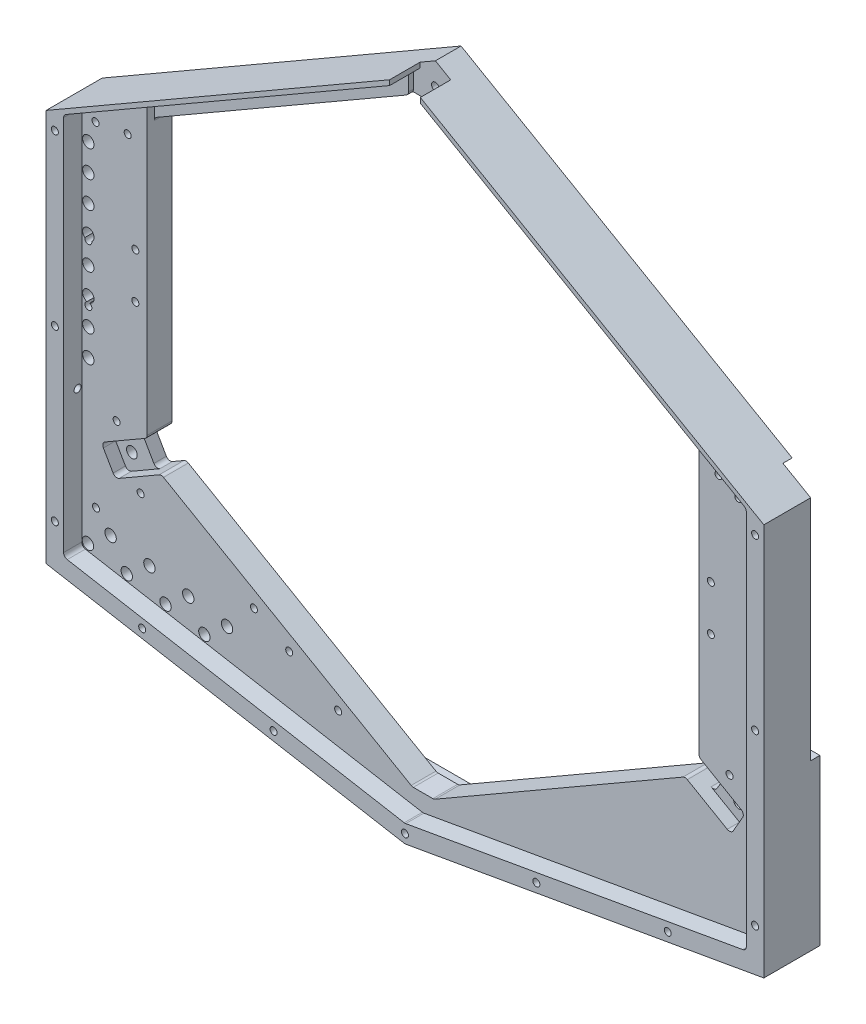
SolidWorks part; units mm, degrees
material "Copper"
ref_plane "Front Plane" through (0, 0, 0) normal (0, 0, 1) x (1, 0, 0)
ref_plane "Top Plane" through (0, 0, 0) normal (0, 1, 0) x (1, 0, 0)
ref_plane "Right Plane" through (0, 0, 0) normal (1, 0, 0) x (0, 0, -1)
sketch "Sketch2" plane through (0, 0, 0) normal (0, 0, 1) x (1, 0, 0)
  line L0 (-81.94, 26.6174) -> (0, 73.9255)
  line L1 (0, 73.9255) -> (81.94, 26.6174)
  line L2 (81.94, 26.6174) -> (81.94, -62.9963)
  line L3 (81.94, -62.9963) -> (0, -77.4445)
  line L4 (0, -77.4445) -> (-81.94, -62.9963)
  line L5 (-81.94, -62.9963) -> (-81.94, 26.6174)
  dimension "D1" = 120
  dimension "D2" = 120
  dimension "D3" = 160
  dimension "D4" = 151.37
  dimension "D5" = 163.88
extrude "Outline" add sketch "Sketch2" against normal blind 12.8
sketch "Sketch3" plane through (0, 0, 0) normal (0, 0, 1) x (1, 0, 0)
  line L0 (-77.94, 27.7721) -> (0, 72.7708)
  line L1 (0, 72.7708) -> (77.94, 27.7721)
  line L2 (77.94, 27.7721) -> (77.94, -59.6399)
  line L3 (77.94, -59.6399) -> (0, -73.3828)
  line L4 (0, -73.3828) -> (-77.94, -59.6399)
  line L5 (-77.94, -59.6399) -> (-77.94, 27.7721)
  line L12 (0, 73.9255) -> (-81.94, 26.6174) construction
  line L14 (0, -77.4445) -> (81.94, -62.9963) construction
  line L15 (-81.94, -62.9963) -> (0, -77.4445) construction
  line L16 (81.94, 26.6174) -> (0, 73.9255) construction
  line L17 (81.94, -62.9963) -> (81.94, 26.6174) construction
  line L18 (-81.94, 26.6174) -> (-81.94, -62.9963) construction
  dimension "D1" = 1
  dimension "D2" = 1
  dimension "D3" = 4
  dimension "D4" = 4
  dimension "D5" = 4
  dimension "D6" = 4
extrude "Inside Cutout" cut sketch "Sketch3" against normal blind 4.14
sketch "Reference Center Line" plane through (0, 0, -4.14) normal (0, 0, 1) x (1, 0, 0)
  line L0 (0, 73.9255) -> (0, -77.4445) construction
  line L1 (-62.3538, 35.1699) -> (0, 71.1699) construction
  line L2 (0, -70.1165) -> (62.3538, -34.1165) construction
  line L3 (62.3538, -34.1165) -> (62.3538, 37.8835) construction
  line L4 (62.3538, 37.8835) -> (0, 73.8835) construction
  line L5 (0, 73.8835) -> (-62.3538, 37.8835) construction
  line L6 (-62.3538, 37.8835) -> (-62.3538, -34.1165) construction
  line L7 (-62.3538, -34.1165) -> (0, -70.1165) construction
  line L8 (0, 71.1699) -> (62.3538, 35.1699) construction
  line L9 (-3.4641, 69.1699) -> (3.4641, 69.1699) construction
  line L11 (-46, 33.8928) -> (46, 33.8928) construction
  line L12 (-46, 33.8928) -> (-46, -62.2855) construction
  line L13 (-46, -62.2855) -> (46, -62.2855) construction
  line L14 (46, 33.8928) -> (46, -62.2855) construction
  circle A0 centre (0, 1.8835) radius 62.3538 construction
  circle A1 centre (0, 1.8835) radius 0.4741 construction
  point P22 (0, 33.8928)
  dimension "D1" = 72
  dimension "D2" = 72.042
  dimension "D3" = 2.35
  dimension "D4" = 2
  dimension "D5" = 92
sketch "Sketch5" plane through (0, 0, -12.8) normal (0, 0, -1) x (-1, 0, 0)
  line L0 (0, -70.8942) -> (-63, -34.5211)
  line L1 (-63, -34.5211) -> (-63, 31.7789)
  line L2 (5, 65.2652) -> (5, 69.884)
  line L3 (0, 0) -> (0, 50) construction
  line L6 (5, 69.884) -> (0, 72.7708)
  line L8 (0, 72.7708) -> (77.94, 27.7721) construction
  line L9 (63, 31.7789) -> (63, -34.5211)
  line L10 (63, -34.5211) -> (0, -70.8942)
  line L11 (0, 72.7708) -> (-5, 69.884)
  line L21 (5, 65.2652) -> (63, 31.7789)
  line L32 (0, 73.9255) -> (0, -77.4445) construction
  line L33 (-5, 69.884) -> (-5, 65.2652)
  line L34 (-77.94, 27.7721) -> (0, 72.7708) construction
  line L35 (-63, 31.7789) -> (-5, 65.2652)
  line L36 (0, 73.9255) -> (0, 1.8855) construction
  line L37 (0, 1.8855) -> (69.308, -38.1295) construction
  line L38 (0, 1.8855) -> (-69.308, -38.1295) construction
  dimension "D1" = 4
  dimension "D2" = 10
  dimension "D3" = 126
  dimension "D4" = 66.3
  dimension "D5" = 66.3
  dimension "D6" = 5
  dimension "D7" = 50
  dimension "D8" = 72.04
  dimension "D9" = 120
  dimension "D10" = 120
  dimension "D11" = 80.03
  dimension "D12" = 80.03
extrude "Cut for Spring Base" cut sketch "Sketch5" against normal through all
sketch "Sketch7" plane through (0, 0, -12.8) normal (0, 0, -1) x (-1, 0, 0)
  line L0 (-5, 69.884) -> (0, 72.7708)
  line L2 (0, 72.7708) -> (5, 69.884)
  line L4 (5, 69.884) -> (5, 60.7708)
  line L5 (5, 60.7708) -> (-5, 60.7708)
  line L6 (-5, 60.7708) -> (-5, 69.884)
  line L7 (-77.94, 27.7721) -> (0, 72.7708) construction
  line L8 (0, 73.9255) -> (0, -77.4445) construction
  line L9 (-77.94, 27.7721) -> (-5, 69.884) construction
  line L10 (5, 69.884) -> (77.94, 27.7721) construction
  dimension "D2" = 12
  dimension "D3" = 10
extrude "J Flex Mounting Point" add sketch "Sketch7" against normal offset from surface (5.85 mm away) 2.81 up to face at (0, 4.0573, -4.14)
sketch "Sketch6" plane through (0, 0, -12.8) normal (0, 0, -1) x (-1, 0, 0)
  line L0 (-67.5, 33.7996) -> (-67.5, -37.6965)
  line L2 (10, -70.8942) -> (67.5, -37.6965)
  line L3 (67.5, -37.6965) -> (67.5, 33.7996)
  line L9 (-10, -70.8942) -> (0, -70.8942)
  line L10 (-63, 31.7789) -> (-63, -34.5211) construction
  line L11 (63, -34.5211) -> (63, 31.7789) construction
  line L12 (0, -70.8942) -> (63, -34.5211) construction
  line L19 (67.5, 33.7996) -> (0, 72.7708)
  line L20 (77.94, 27.7721) -> (0, 72.7708) construction
  line L21 (0, 72.7708) -> (-77.94, 27.7721) construction
  line L22 (0, 72.7708) -> (-67.5, 33.7996)
  line L47 (0, -70.8942) -> (10, -70.8942)
  line L48 (-67.5, -37.6965) -> (-10, -70.8942)
  line L50 (-63, -34.5211) -> (0, -70.8942) construction
  line L52 (0, 73.9255) -> (0, -77.4445) construction
  dimension "D1" = 4.5
  dimension "D2" = 4.5
  dimension "D3" = 5
  dimension "D4" = 5
extrude "Spring Base Mounting Cut" cut sketch "Sketch6" against normal blind 3
sketch "Sketch9" plane through (0, 0, 0) normal (0, 0, 1) x (1, 0, 0)
  line L2 (3.5, 71.9048) -> (3.5, 70.7501)
  line L3 (77.94, 27.7721) -> (0, 72.7708) construction
  line L4 (3.5, 70.7501) -> (0, 72.7708)
  line L5 (0, 72.7708) -> (-3.5, 70.7501)
  line L6 (0, 72.7708) -> (-77.94, 27.7721) construction
  line L7 (-3.5, 70.7501) -> (-3.5, 71.9048)
  line L10 (-3.5, 71.9048) -> (0, 73.9255)
  line L11 (0, 73.9255) -> (0, -77.4445) construction
  line L12 (0, 73.9255) -> (3.5, 71.9048)
  line L14 (0, 73.9255) -> (-81.94, 26.6174) construction
  dimension "D1" = 7
extrude "Central Copper Flex cutout" cut sketch "Sketch9" against normal up to surface (6.95 mm away) up to face at (0, 66.373, -6.95)
hole_wizard "M2 Tap Drill for Backplate" positions "Sketch10" profile "Sketch11" hole size "M2x0.4" standard "ANSI Metric"
sketch "Sketch10" plane through (0, 0, -9.8) normal (0, 0, -1) x (-1, 0, 0)
  line L0 (-65, 24.3042) -> (-65, -35.6758) construction
  line L1 (-65, -35.6758) -> (-4, -70.8942) construction
  line L2 (-10, -70.8942) -> (10, -70.8942) construction
  line L4 (4, -70.8942) -> (65, -35.6758) construction
  line L5 (65, -35.6758) -> (65, 24.3242) construction
  line L7 (-63, -34.5211) -> (-63, 31.7789) construction
  line L8 (63, 31.7789) -> (63, -34.5211) construction
  line L9 (63, -34.5211) -> (0, -70.8942) construction
  line L10 (0, -70.8942) -> (-63, -34.5211) construction
  line L29 (-62.3538, 33.884) -> (0, 69.884) construction
  line L30 (-62.3538, -34.1165) -> (-62.3538, 37.8835) construction
  line L31 (0, 73.9255) -> (0, -77.4445) construction
  line L32 (0, 69.884) -> (62.3538, 33.884) construction
  line L33 (62.3538, 37.8835) -> (62.3538, -34.1165) construction
  line L36 (5, 65.2652) -> (63, 31.7789) construction
  line L37 (-63, 31.7789) -> (-5, 65.2652) construction
  line L38 (-63, -34.5211) -> (-67.5, -37.6965) construction
  point P0 (-65, 24.3042)
  point P2 (-41.1362, 46.134)
  point P4 (-19.4856, 58.634)
  point P6 (19.4856, 58.634)
  point P8 (41.1362, 46.134)
  point P10 (65, 24.3242)
  point P12 (65, 1.8242)
  point P14 (65, -20.6758)
  point P18 (52.0096, -43.1758)
  point P20 (32.9571, -54.1758)
  point P22 (15.6366, -64.1758)
  point P24 (-15.6366, -64.1758)
  point P26 (-32.9571, -54.1758)
  point P28 (-52.0096, -43.1758)
  point P32 (-65, -20.6958)
  point P35 (-65, 1.8042)
  dimension "D1" = 2
  dimension "D2" = 2
  dimension "D3" = 2
  dimension "D4" = 2
  dimension "D5" = 14.98
  dimension "D6" = 22.5
  dimension "D7" = 22.5
  dimension "D8" = 15
  dimension "D9" = 22
  dimension "D10" = 20
  dimension "D11" = 20
  dimension "D12" = 22
  dimension "D13" = 15
  dimension "D14" = 22.5
  dimension "D15" = 22.5
  dimension "D16" = 15
  dimension "D17" = 1.5
  dimension "D18" = 22.5
  dimension "D19" = 25
  dimension "D20" = 22.5
  dimension "D21" = 25
sketch "Sketch11" plane through (65, 24.3042, -9.8) normal (1, 0, 0) x (0, 1, 0)
  line L0 (0, 0) -> (0, 3.9807)
  line L1 (0, 3.9807) -> (0.8, 3.5)
  line L2 (0.8, 3.5) -> (0.8, 0)
  line L5 (0.8, 0) -> (0, 0)
  line L10 (0, 3.9807) -> (-0.8, 3.5) construction
  line L11 (0, -6.35) -> (0, 107.95) construction
  dimension "Hole Dia." = 1.6
  dimension "Hole Depth" = 3.5
  dimension "Drill Angle" = 118
sketch "Sketch12" plane through (0, 0, -12.8) normal (0, 0, -1) x (-1, 0, 0)
  line L0 (10, -70.8942) -> (67.5, -37.6965) construction
  line L1 (64, -39.7172) -> (67.5, -37.6965)
  line L2 (67.5, -37.6965) -> (67.5, -33.6551)
  line L3 (67.5, -37.6965) -> (67.5, 33.7996) construction
  line L4 (67.5, -33.6551) -> (74.4462, -37.6654)
  line L5 (74.4462, -37.6654) -> (70.9462, -43.7276)
  line L6 (70.9462, -43.7276) -> (64, -39.7172)
  line L7 (-67.5, -33.6551) -> (-67.5, -37.6965)
  line L8 (-67.5, 33.7996) -> (-67.5, -37.6965) construction
  line L9 (-67.5, -37.6965) -> (-64, -39.7172)
  line L10 (-67.5, -37.6965) -> (-10, -70.8942) construction
  line L11 (-64, -39.7172) -> (-70.9462, -43.7276)
  line L12 (-70.9462, -43.7276) -> (-74.4462, -37.6654)
  line L13 (-74.4462, -37.6654) -> (-67.5, -33.6551)
  dimension "D1" = 60
  dimension "D2" = 6
  dimension "D3" = 7
  dimension "D4" = 6
  dimension "D5" = 7
extrude "Outer Copper Flex cutouts" cut sketch "Sketch12" against normal up to surface (3 mm away) up to face at (64.2, 24.3042, -9.8)
hole_wizard "#2 Clearance Holes for Flex Feet" positions "Sketch13" profile "Sketch14" hole size "#2" standard "ANSI Inch"
sketch "Sketch13" plane through (0, 0, -9.8) normal (0, 0, -1) x (-1, 0, 0)
  line L1 (0, 1.8835) -> (69.3037, -38.129) construction
  line L3 (0, 1.8835) -> (-69.308, -38.1315) construction
  line L5 (0, 73.9255) -> (0, -77.4445) construction
  point P0 (69.3037, -38.129)
  point P3 (-69.308, -38.1315)
  point P6 (0, 68.6855)
  point P29 (0, 0)
  dimension "D1" = 66.802
  dimension "D2" = 80.025
  dimension "D3" = 60
  dimension "D4" = 60
  dimension "D5" = 80.03
sketch "Sketch14" plane through (-69.3037, -38.129, -9.8) normal (1, 0, 0) x (0, 1, 0)
  line L0 (0, 0) -> (0, 5.66)
  line L1 (0, 5.66) -> (1.2192, 5.66)
  line L2 (1.2192, 5.66) -> (1.2192, 0)
  line L5 (1.2192, 0) -> (0, 0)
  line L11 (0, -6.35) -> (0, 107.95) construction
  dimension "Thru Hole Dia." = 2.4384
  dimension "Thru Hole Depth" = 5.66
sketch "Sketch15" plane through (0, 0, -4.14) normal (0, 0, 1) x (1, 0, 0)
  line L0 (-63, -30.7945) -> (-73.5018, -36.8577)
  line L1 (-63, 31.7789) -> (-63, -34.5211) construction
  line L2 (-73.5018, -36.8577) -> (-70.2745, -42.4476)
  line L3 (-70.2745, -42.4476) -> (-59.7727, -36.3844)
  line L4 (-63, -34.5211) -> (0, -70.8942) construction
  line L5 (-59.7727, -36.3844) -> (-63, -34.5211)
  line L6 (-63, -34.5211) -> (-63, -30.7945)
  line L7 (-64.6136, -31.7262) -> (-61.3864, -37.316) construction
  line L8 (63, -34.5211) -> (63, -30.8575)
  line L9 (63, -34.5211) -> (63, 31.7789) construction
  line L10 (63, -30.8575) -> (73.4788, -36.9075)
  line L11 (73.4788, -36.9075) -> (70.3061, -42.4028)
  line L12 (70.3061, -42.4028) -> (59.8273, -36.3529)
  line L13 (0, -70.8942) -> (63, -34.5211) construction
  line L14 (59.8273, -36.3529) -> (63, -34.5211)
  point P12 (-63, -34.5211)
  dimension "D1" = 3.2
  dimension "D2" = 3
  dimension "D3" = 3.2
  dimension "D4" = 3
extrude "Channels for Outer Flex" cut sketch "Sketch15" against normal up to surface (2.81 mm away) up to face at (0, 68.2796, -6.95)
sketch "Sketch17" plane through (0, 0, -9.8) normal (0, 0, -1) x (-1, 0, 0)
  line L0 (-65, 1.8042) -> (-65, -20.6958) construction
  line L1 (65, -20.6758) -> (65, 1.8242) construction
  circle A0 centre (-65, -9.4458) radius 0.8
  circle A1 centre (65, -9.4258) radius 0.8
  dimension "D1" = 1.6
  dimension "D2" = 1.6
extrude "Optional Alignment Pins" cut sketch "Sketch17" against normal blind 3
sketch "SMA Reference Sketch" plane through (0, 0, -12.8) normal (0, 0, -1) x (-1, 0, 0)
  line L14 (81.94, 26.6174) -> (81.94, -62.9963) construction
  line L21 (73.8944, 19.163) -> (78.9856, 14.0718) construction
  line L22 (73.8944, 23.663) -> (78.9856, 18.5718) construction
  line L23 (73.8944, 14.663) -> (78.9856, 9.5718) construction
  line L24 (73.8944, 10.163) -> (78.9856, 5.0718) construction
  line L25 (72.1444, -32.8014) -> (77.2356, -37.8926) construction
  line L26 (-73.8944, 20.0718) -> (-78.9856, 25.163) construction
  line L27 (-81.94, -62.9963) -> (-81.94, 26.6174) construction
  line L28 (-73.8944, 15.5718) -> (-78.9856, 20.663) construction
  line L29 (-73.8944, 11.0718) -> (-78.9856, 16.163) construction
  line L30 (-73.8944, 6.5718) -> (-78.9856, 11.663) construction
  line L31 (59.1444, -57.3926) -> (64.2356, -52.3014) construction
  line L32 (72.1444, -50.8926) -> (77.2356, -45.8014) construction
  line L33 (72.1444, -93.8926) -> (77.2356, -88.8014) construction
  line L34 (-73.8944, 2.0718) -> (-78.9856, 7.163) construction
  line L35 (-73.8944, -2.4282) -> (-78.9856, 2.663) construction
  line L36 (-73.8944, -6.9282) -> (-78.9856, -1.837) construction
  line L37 (-73.8944, -11.4282) -> (-78.9856, -6.337) construction
  line L38 (73.8944, 5.663) -> (78.9856, 0.5718) construction
  line L39 (73.8944, 1.163) -> (78.9856, -3.9282) construction
  line L40 (73.8944, -3.337) -> (78.9856, -8.4282) construction
  line L41 (73.8944, -7.837) -> (78.9856, -12.9282) construction
  circle A0 centre (73.8944, 23.663) radius 0.95 construction
  circle A1 centre (78.9856, 18.5718) radius 0.95 construction
  circle A2 centre (76.44, 21.1174) radius 1.3 construction
  circle A3 centre (73.8944, 19.163) radius 0.95 construction
  circle A4 centre (78.9856, 14.0718) radius 0.95 construction
  circle A5 centre (76.44, 16.6174) radius 1.3 construction
  circle A6 centre (73.8944, 14.663) radius 0.95 construction
  circle A7 centre (78.9856, 9.5718) radius 0.95 construction
  circle A8 centre (76.44, 12.1174) radius 1.3 construction
  circle A9 centre (73.8944, 10.163) radius 0.95 construction
  circle A10 centre (78.9856, 5.0718) radius 0.95 construction
  circle A11 centre (76.44, 7.6174) radius 1.3 construction
  circle A12 centre (72.1444, -32.8014) radius 0.95 construction
  circle A13 centre (77.2356, -37.8926) radius 0.95 construction
  circle A14 centre (74.69, -35.347) radius 1.3 construction
  circle A15 centre (-76.44, 22.6174) radius 1.3 construction
  circle A16 centre (-78.9856, 25.163) radius 0.95 construction
  circle A17 centre (-73.8944, 20.0718) radius 0.95 construction
  circle A18 centre (-76.44, 18.1174) radius 1.3 construction
  circle A19 centre (-78.9856, 20.663) radius 0.95 construction
  circle A20 centre (-73.8944, 15.5718) radius 0.95 construction
  circle A21 centre (-76.44, 13.6174) radius 1.3 construction
  circle A22 centre (-78.9856, 16.163) radius 0.95 construction
  circle A23 centre (-73.8944, 11.0718) radius 0.95 construction
  circle A24 centre (-76.44, 9.1174) radius 1.3 construction
  circle A25 centre (-78.9856, 11.663) radius 0.95 construction
  circle A26 centre (-73.8944, 6.5718) radius 0.95 construction
  circle A27 centre (61.69, -54.847) radius 1.3 construction
  circle A28 centre (64.2356, -52.3014) radius 0.95 construction
  circle A29 centre (59.1444, -57.3926) radius 0.95 construction
  circle A30 centre (72.1444, -50.8926) radius 0.95 construction
  circle A31 centre (77.2356, -45.8014) radius 0.95 construction
  circle A32 centre (74.69, -48.347) radius 1.3 construction
  circle A33 centre (74.69, -91.347) radius 1.3 construction
  circle A34 centre (77.2356, -88.8014) radius 0.95 construction
  circle A35 centre (72.1444, -93.8926) radius 0.95 construction
  circle A36 centre (74.69, -35.347) radius 43 construction
  circle A37 centre (74.69, -48.347) radius 13 construction
  circle A38 centre (61.69, -54.847) radius 43 construction
  circle A39 centre (74.69, -91.347) radius 43 construction
  circle A40 centre (76.44, 21.1174) radius 13 construction
  circle A41 centre (-76.44, 4.6174) radius 1.3 construction
  circle A42 centre (-78.9856, 7.163) radius 0.95 construction
  circle A43 centre (-73.8944, 2.0718) radius 0.95 construction
  circle A44 centre (-76.44, 0.1174) radius 1.3 construction
  circle A45 centre (-78.9856, 2.663) radius 0.95 construction
  circle A46 centre (-73.8944, -2.4282) radius 0.95 construction
  circle A47 centre (-76.44, -4.3826) radius 1.3 construction
  circle A48 centre (-78.9856, -1.837) radius 0.95 construction
  circle A49 centre (-73.8944, -6.9282) radius 0.95 construction
  circle A50 centre (-76.44, -8.8826) radius 1.3 construction
  circle A51 centre (-78.9856, -6.337) radius 0.95 construction
  circle A52 centre (-73.8944, -11.4282) radius 0.95 construction
  circle A53 centre (73.8944, 5.663) radius 0.95 construction
  circle A54 centre (78.9856, 0.5718) radius 0.95 construction
  circle A55 centre (76.44, 3.1174) radius 1.3 construction
  circle A56 centre (73.8944, 1.163) radius 0.95 construction
  circle A57 centre (78.9856, -3.9282) radius 0.95 construction
  circle A58 centre (76.44, -1.3826) radius 1.3 construction
  circle A59 centre (73.8944, -3.337) radius 0.95 construction
  circle A60 centre (78.9856, -8.4282) radius 0.95 construction
  circle A61 centre (76.44, -5.8826) radius 1.3 construction
  circle A62 centre (73.8944, -7.837) radius 0.95 construction
  circle A63 centre (78.9856, -12.9282) radius 0.95 construction
  circle A64 centre (76.44, -10.3826) radius 1.3 construction
  point P10 (76.44, 16.6174)
  point P20 (76.44, 21.1174)
  point P25 (76.44, 12.1174)
  point P32 (76.44, 7.6174)
  point P37 (74.69, -35.347)
  point P120 (76.44, 3.1174)
  point P127 (76.44, -1.3826)
  point P134 (76.44, -5.8826)
  point P141 (76.44, -10.3826)
  dimension "D5" = 1.9
  dimension "D2" = 2.6
  dimension "D3" = 8
  dimension "D10" = 2.6
  dimension "D11" = 1.9
  dimension "D12" = 1.9
  dimension "D18" = 26
  dimension "D23" = 86
  dimension "D26" = 4.5
  dimension "D27" = 4.5
  dimension "D28" = 4.5
  dimension "D29" = 43
  dimension "D30" = 13
  dimension "D31" = 26
  dimension "D1" = 7.2
  dimension "D4" = 4.5
  dimension "D6" = 5.5
  dimension "D7" = 5.5
  dimension "D8" = 45
  dimension "D9" = 7.25
  dimension "D13" = 7.2
  dimension "D14" = 5.5
  dimension "D15" = 4
  dimension "D16" = 45
  dimension "D19" = 7.25
  dimension "D20" = 45
  dimension "D21" = 4.5
  dimension "D22" = 7.25
  dimension "D24" = 13
  dimension "D25" = 43
  dimension "D17" = 8
sketch "Sketch19" plane through (0, 0, -12.8) normal (0, 0, -1) x (-1, 0, 0)
  line L1 (81.94, -62.9963) -> (0, -77.4445) construction
  circle A0 centre (76.44, 21.1174) radius 1.3
  circle A12 centre (-76.44, 22.6174) radius 1.3
  circle A22 centre (-76.44, 16.5174) radius 1.3
  circle A23 centre (-76.44, 10.4174) radius 1.3
  circle A24 centre (-76.44, 4.3174) radius 1.3
  circle A25 centre (-76.44, -1.7826) radius 1.3
  circle A26 centre (-76.44, -7.8826) radius 1.3
  circle A27 centre (-76.44, -13.9826) radius 1.3
  circle A28 centre (-76.44, -20.0826) radius 1.3
  circle A29 centre (76.44, 15.0174) radius 1.3
  circle A30 centre (76.44, 8.9174) radius 1.3
  circle A31 centre (76.44, 2.8174) radius 1.3
  circle A32 centre (76.44, -3.2826) radius 1.3
  circle A33 centre (76.44, -9.3826) radius 1.3
  circle A34 centre (76.44, -15.4826) radius 1.3
  circle A35 centre (76.44, -21.5826) radius 1.3
  circle A36 centre (49.94, -63.0539) radius 1.3
  circle A44 centre (44.763, -58.8896) radius 1.3
  circle A50 centre (53.6263, -57.3268) radius 1.3
  circle A51 centre (58.8033, -61.4911) radius 1.3
  circle A52 centre (62.4895, -55.7639) radius 1.3
  circle A53 centre (67.6665, -59.9282) radius 1.3
  circle A54 centre (71.3528, -54.2011) radius 1.3
  circle A55 centre (76.5298, -58.3654) radius 1.3
  dimension "D1" = 2.6
  dimension "D2" = 8
  dimension "D3" = 8
  dimension "D4" = 5.5
  dimension "D5" = 32
  dimension "D6" = 4
  dimension "D7" = 10.5
  dimension "D8" = 6.644
extrude "SMA_Lines" cut sketch "Sketch19" against normal up to next
sketch "Sketch20" plane through (0, 0, -12.8) normal (0, 0, -1) x (-1, 0, 0)
  line L0 (67.5, 23.8447) -> (73.0812, 29.4259)
  line L1 (67.5, -33.6551) -> (67.5, 33.7996) construction
  line L2 (42.44, -52.1649) -> (37.6769, -54.9149)
  line L3 (73.0812, 29.4259) -> (81.94, 20.5672)
  line L4 (81.94, 20.5672) -> (81.94, -62.9963)
  line L5 (81.94, -62.9963) -> (42.44, -69.9612)
  line L6 (81.94, -62.9963) -> (0, -77.4445) construction
  line L8 (10, -70.8942) -> (64, -39.7172) construction
  line L9 (10, -70.8942) -> (64, -39.7172) construction
  line L10 (42.44, -52.1649) -> (64, -39.7172)
  line L11 (64, -39.7172) -> (67.5, -33.6551)
  line L12 (67.5, -33.6551) -> (74.4462, -37.6654) construction
  line L13 (67.5, -33.6551) -> (67.5, 23.8447)
  line L14 (-75.6096, 30.2723) -> (-67.5, 22.1627)
  line L15 (-81.94, 26.6174) -> (0, 73.9255) construction
  line L16 (-67.5, 33.7996) -> (-67.5, -33.6551) construction
  line L17 (-67.5, 22.1627) -> (-67.5, -25.3826)
  line L18 (-67.5, -25.3826) -> (-81.94, -25.3826)
  line L20 (-81.94, -62.9963) -> (-81.94, 26.6174) construction
  line L21 (-81.94, -25.3826) -> (-81.94, 26.6174)
  line L22 (-81.94, 26.6174) -> (-75.6096, 30.2723)
  line L23 (73.8944, 23.663) -> (78.9856, 18.5718) construction
  line L24 (-73.8944, 20.0718) -> (-78.9856, 25.163) construction
  line L25 (37.6769, -54.9149) -> (37.6769, -58.9149)
  line L26 (37.6769, -58.9149) -> (42.44, -58.9149)
  line L28 (42.44, -58.9149) -> (42.44, -69.9612)
  dimension "D2" = 8.25
  dimension "D3" = 6
  dimension "D4" = 34.5
  dimension "D5" = 3.5
extrude "SMA Cutaway" cut sketch "Sketch20" against normal offset from surface (2.11 mm away) 6.55 up to face at (77.74, 22.6174, -4.14)
fillet "Fillet4" radius 3 2 edges at (-73.0812, 29.4259, -11.745) (-37.6769, -58.9149, -11.745)
hole_wizard "M2x0.4 Tapped for SMAs" positions "Sketch21" profile "Sketch22" hole size "M2x0.4" standard "ANSI Metric"
sketch "Sketch21" plane through (0, 0, -10.69) normal (0, 0, -1) x (-1, 0, 0)
  circle A0 centre (76.44, 21.1174) radius 1.3 construction
  circle A1 centre (-76.44, 22.6174) radius 1.3 construction
  circle A2 centre (49.94, -63.0539) radius 1.3 construction
  circle A3 centre (44.763, -58.8896) radius 1.3 construction
  point P72 (73.895, 23.6624)
  point P74 (78.985, 18.5724)
  point P90 (-78.985, 25.1624)
  point P92 (-73.895, 20.0724)
  point P108 (-78.985, 19.0624)
  point P109 (-73.895, 13.9724)
  point P110 (-78.985, 12.9624)
  point P111 (-73.895, 7.8724)
  point P112 (-78.985, 6.8624)
  point P113 (-73.895, 1.7724)
  point P114 (-78.985, 0.7624)
  point P115 (-73.895, -4.3276)
  point P116 (-78.985, -5.3376)
  point P117 (-73.895, -10.4276)
  point P118 (-78.985, -11.4376)
  point P119 (-73.895, -16.5276)
  point P120 (-78.985, -17.5376)
  point P121 (-73.895, -22.6276)
  point P138 (73.895, 17.5624)
  point P139 (78.985, 12.4724)
  point P140 (73.895, 11.4624)
  point P141 (78.985, 6.3724)
  point P142 (73.895, 5.3624)
  point P143 (78.985, 0.2724)
  point P144 (73.895, -0.7376)
  point P145 (78.985, -5.8276)
  point P146 (73.895, -6.8376)
  point P147 (78.985, -11.9276)
  point P148 (73.895, -12.9376)
  point P149 (78.985, -18.0276)
  point P150 (73.895, -19.0376)
  point P151 (78.985, -24.1276)
  point P171 (49.315, -59.5089)
  point P173 (50.565, -66.5989)
  point P185 (58.1783, -57.9461)
  point P186 (59.4283, -65.0361)
  point P187 (67.0415, -56.3832)
  point P188 (68.2915, -63.4732)
  point P189 (75.9048, -54.8204)
  point P190 (77.1548, -61.9104)
  point P191 (45.388, -62.4346)
  point P193 (44.138, -55.3446)
  point P202 (54.2513, -60.8718)
  point P203 (53.0013, -53.7818)
  point P204 (63.1145, -59.3089)
  point P205 (61.8645, -52.2189)
  point P206 (71.9778, -57.7461)
  point P207 (70.7278, -50.6561)
  dimension "D4" = 2.545
  dimension "D7" = 2.545
  dimension "D8" = 2.545
  dimension "D9" = 8
  dimension "D14" = 0.625
  dimension "D1" = 2.545
  dimension "D2" = 2.545
  dimension "D3" = 2.545
  dimension "D5" = 2.545
  dimension "D6" = 2.545
  dimension "D11" = 3.545
  dimension "D12" = 0.625
  dimension "D13" = 3.545
  dimension "D16" = 3.545
  dimension "D17" = 0.625
  dimension "D18" = 0.625
  dimension "D19" = 3.545
  dimension "D10" = 8
  dimension "D15" = 4
sketch "Sketch22" plane through (-73.895, 23.6624, -10.69) normal (1, 0, 0) x (0, 1, 0)
  line L0 (0, 0) -> (0, 5.4807)
  line L1 (0, 5.4807) -> (0.8, 5)
  line L2 (0.8, 5) -> (0.8, 0)
  line L5 (0.8, 0) -> (0, 0)
  line L10 (0, 5.4807) -> (-0.8, 5) construction
  line L11 (0, -6.35) -> (0, 107.95) construction
  dimension "Hole Dia." = 1.6
  dimension "Hole Depth" = 5
  dimension "Drill Angle" = 118
sketch "Sketch23" plane through (0, 0, -4.14) normal (0, 0, 1) x (1, 0, 0)
  line L0 (-63, 31.7789) -> (-63, 36.3977)
  line L1 (-3.5, 70.7501) -> (-77.94, 27.7721) construction
  line L2 (-63, 36.3977) -> (-5, 69.884)
  line L3 (-5, 69.884) -> (-5, 65.2652)
  line L4 (-5, 65.2652) -> (-63, 31.7789)
  line L5 (5, 65.2652) -> (5, 69.884)
  line L6 (5, 65.2652) -> (63, 31.7789)
  line L7 (63, 31.7789) -> (63, 36.3977)
  line L8 (77.94, 27.7721) -> (5, 69.884) construction
  line L9 (63, 36.3977) -> (5, 69.884)
extrude "Slight Relief Under Array" cut sketch "Sketch23" against normal blind 1.66
hole_wizard "M2x0.4 Tapped for Radiation Cover" positions "Sketch24" profile "Sketch25" hole size "M2x0.4" standard "ANSI Metric"
sketch "Sketch24" plane through (0, 0, 0) normal (0, 0, 1) x (1, 0, 0)
  line L0 (-81.94, 26.6174) -> (-81.94, -62.9963) construction
  line L1 (-77.94, -59.6399) -> (0, -73.3828) construction
  line L2 (0, -73.3828) -> (77.94, -59.6399) construction
  line L3 (77.94, -59.6399) -> (77.94, 27.7721) construction
  line L4 (81.94, -62.9963) -> (81.94, 26.6174) construction
  line L5 (-79.94, 23.6174) -> (-79.94, -53.6399) construction
  line L6 (0, -77.4445) -> (0, -73.3828) construction
  line L7 (79.94, 23.6174) -> (79.94, -53.6399) construction
  line L8 (0, -73.3828) -> (77.94, -59.6399) construction
  point P0 (-79.94, 23.6174)
  point P2 (-79.94, -53.6399)
  point P4 (-30, -70.1239)
  point P6 (30, -70.1239)
  point P8 (79.94, -53.6399)
  point P10 (79.94, 23.6174)
  point P31 (-79.94, -15.0112)
  point P38 (0, -75.4137)
  point P44 (79.94, -15.0112)
  point P47 (-60, -64.834)
  point P49 (60, -64.834)
  dimension "D1" = 2
  dimension "D2" = 3
  dimension "D3" = 2
  dimension "D4" = 6
  dimension "D5" = 2
  dimension "D6" = 30
  dimension "D7" = 2
  dimension "D8" = 30
  dimension "D9" = 2
  dimension "D10" = 6
  dimension "D11" = 2
  dimension "D12" = 3
  dimension "D13" = 2
  dimension "D14" = 30
  dimension "D15" = 2
  dimension "D16" = 30
sketch "Sketch25" plane through (-79.94, 23.6174, 0) normal (1, 0, 0) x (0, -1, 0)
  line L0 (0, 0) -> (0, 5.4807)
  line L1 (0, 5.4807) -> (0.8, 5)
  line L2 (0.8, 5) -> (0.8, 0)
  line L5 (0.8, 0) -> (0, 0)
  line L10 (0, 5.4807) -> (-0.8, 5) construction
  line L11 (0, -6.35) -> (0, 107.95) construction
  dimension "Hole Dia." = 1.6
  dimension "Hole Depth" = 5
  dimension "Drill Angle" = 118
hole_wizard "M2x0.4 Tap for PCB Mounts" positions "Sketch26" profile "Sketch27" hole size "M2x0.4" standard "ANSI Metric"
sketch "Sketch26" plane through (0, 0, -4.14) normal (0, 0, 1) x (1, 0, 0)
  line L1 (76.44, 22.6174) -> (76.44, 2.1174) construction
  line L6 (74.69, -6.3826) -> (74.69, -18.8826) construction
  line L9 (-76.44, 21.1174) -> (-76.44, 8.1174) construction
  line L11 (-76.44, -4.8826) -> (-76.44, -17.8826) construction
  line L15 (-76.44, -11.3826) -> (-77.94, -11.3826) construction
  line L16 (-77.94, 27.7721) -> (-77.94, -59.6399) construction
  line L18 (-76.44, 14.6174) -> (-77.94, 14.6174) construction
  line L19 (-77.94, 27.7721) -> (-77.94, -59.6399) construction
  line L23 (-76.44, 8.1174) -> (-76.44, -4.8826) construction
  line L24 (-74.69, -56.8826) -> (-74.69, -43.8826) construction
  circle A6 centre (76.44, 22.6174) radius 1.3 construction
  circle A11 centre (-76.44, 21.1174) radius 1.3 construction
  point P0 (76.44, 12.3674)
  point P20 (76.44, 12.3674)
  point P31 (74.69, -12.6326)
  point P34 (74.69, -12.6326)
  point P53 (-76.44, 14.6174)
  point P55 (-76.44, -11.3826)
  point P57 (-74.69, -50.3826)
  point P59 (-19.3942, -62.8516)
  point P78 (-76.44, 14.6174)
  point P79 (-76.44, -11.3826)
  point P95 (-76.44, 1.6174)
  point P106 (-67.45, 27.1118)
  point P108 (-65.6984, 5.1456)
  point P110 (-65.6984, -5.1874)
  point P112 (-69.9656, -30.8826)
  point P114 (-64.5046, -42.4348)
  point P116 (-38.622, -52.2344)
  point P118 (-30.5702, -56.7556)
  point P140 (71.9662, 24.8501)
  point P150 (74.69, -0.1326)
  point P153 (69.97, -30.8826)
  point P159 (67.45, 27.1118)
  point P161 (65.7, 5.1456)
  point P163 (65.7, -5.1874)
  point P174 (-74.7882, 25.8367)
  dimension "D8" = 0.3048
  dimension "D11" = 10.1854
  dimension "D2" = 5
  dimension "D3" = 8.99
  dimension "D4" = 5.9944
  dimension "D7" = 2.9718
  dimension "8.99" = 8.99
  dimension "D22" = 0
  dimension "D23" = 5
sketch "Sketch27" plane through (76.44, 12.3674, -4.14) normal (1, 0, 0) x (0, -1, 0)
  line L0 (0, 0) -> (0, 5.1807)
  line L1 (0, 5.1807) -> (0.8, 4.7)
  line L2 (0.8, 4.7) -> (0.8, 0)
  line L5 (0.8, 0) -> (0, 0)
  line L10 (0, 5.1807) -> (-0.8, 4.7) construction
  line L11 (0, -6.35) -> (0, 107.95) construction
  dimension "Hole Dia." = 1.6
  dimension "Hole Depth" = 4.7
  dimension "Drill Angle" = 118
hole_wizard "Tap Drill for M3x0.5 Tap1" positions "Sketch28" profile "Sketch29" hole size "M3x0.5" standard "ANSI Metric"
sketch "Sketch28" plane through (0, 0, -12.8) normal (0, 0, -1) x (-1, 0, 0)
  line L0 (-69.3538, 29.7708) -> (69.3538, 29.7708) construction
  line L2 (-40, -61.4445) -> (40, -61.4445) construction
  line L4 (0, 73.9255) -> (0, -77.4445) construction
  line L6 (5, 60.7708) -> (-5, 60.7708) construction
  line L7 (-62.3538, -34.1165) -> (-62.3538, 37.8835) construction
  point P0 (-69.3538, 29.7708)
  point P2 (69.3538, 29.7708)
  point P4 (40, -61.4445)
  point P6 (-40, -61.4445)
  point P17 (0, 29.7708)
  point P20 (0, -61.4445)
  dimension "D1" = 40
  dimension "D2" = 16
  dimension "D3" = 7
  dimension "D4" = 31
sketch "Sketch29" plane through (69.3538, 29.7708, -12.8) normal (1, 0, 0) x (0, 1, 0)
  line L0 (0, 0) -> (0, 6.7511)
  line L1 (0, 6.7511) -> (1.25, 6)
  line L2 (1.25, 6) -> (1.25, 0)
  line L5 (1.25, 0) -> (0, 0)
  line L10 (0, 6.7511) -> (-1.25, 6) construction
  line L11 (0, -6.35) -> (0, 107.95) construction
  dimension "Hole Dia." = 2.5
  dimension "Hole Depth" = 6
  dimension "Drill Angle" = 118
sketch "Sketch33" plane through (0, 0, -6.95) normal (0, 0, 1) x (1, 0, 0)
  line L0 (-67.0066, -33.1077) -> (-63.7793, -38.6976)
  line L1 (-67.0066, -33.1077) -> (-61.8104, -30.1077)
  line L2 (-63.7793, -38.6976) -> (-58.5831, -35.6976)
  line L3 (-61.8104, -30.1077) -> (-58.5831, -35.6976)
  line L4 (-73.5018, -36.8577) -> (-63, -30.7945) construction
  line L5 (-59.7727, -36.3844) -> (-70.2745, -42.4476) construction
  line L6 (-70.2745, -42.4476) -> (-73.5018, -36.8577) construction
  line L7 (66.9836, -33.1575) -> (63.8109, -38.6528)
  line L8 (66.9836, -33.1575) -> (61.7875, -30.1575)
  line L9 (63.8109, -38.6528) -> (58.6147, -35.6528)
  line L10 (61.7875, -30.1575) -> (58.6147, -35.6528)
  line L13 (73.4788, -36.9075) -> (70.3061, -42.4028) construction
  line L15 (-6.4904, 64.4048) -> (-6.4904, 58.4048)
  line L16 (6.4904, 64.4048) -> (6.4904, 58.4048)
  line L17 (-6.4904, 58.4048) -> (6.4904, 58.4048)
  line L18 (-3.5, 71.9048) -> (3.5, 71.9048)
  line L20 (-63, 31.7789) -> (-5, 65.2652) construction
  line L21 (5, 65.2652) -> (63, 31.7789) construction
  line L22 (-6.4904, 64.4048) -> (-5, 65.2652)
  line L23 (-5, 65.2652) -> (5, 65.2652)
  line L24 (5, 65.2652) -> (6.4904, 64.4048)
  dimension "D1" = 7.5
  dimension "D2" = 7.5
  dimension "D3" = 6
  dimension "D4" = 0
  dimension "D5" = 0
  dimension "D6" = 6
  dimension "D7" = 6
extrude "Cut-Extrude1" cut sketch "Sketch33" against normal blind 30
hole_wizard "M2x0.4 Tap for Thermometer" positions "Sketch30" profile "Sketch31" hole size "M2x0.4" standard "ANSI Metric"
sketch "Sketch30" plane through (-81.94, 0, 0) normal (-1, 0, 0) x (0, 0, 1)
  line L0 (-10.69, -62.9963) -> (0, -62.9963) construction
  line L1 (-10.69, -62.9963) -> (-10.69, 20.5672) construction
  circle A0 centre (-3.19, -27.9963) radius 7.15 construction
  point P0 (-3.19, -27.9963)
  dimension "D1" = 35
  dimension "D2" = 7.5
sketch "Sketch31" plane through (-81.94, -27.9963, -3.19) normal (0, 1, 0) x (0, 0, 1)
  line L0 (0, 0) -> (0, 5.4807)
  line L1 (0, 5.4807) -> (0.8, 5)
  line L2 (0.8, 5) -> (0.8, 0)
  line L5 (0.8, 0) -> (0, 0)
  line L10 (0, 5.4807) -> (-0.8, 5) construction
  line L11 (0, -6.35) -> (0, 107.95) construction
  dimension "Hole Dia." = 1.6
  dimension "Hole Depth" = 5
  dimension "Drill Angle" = 118
fillet "Fillet1" radius 1 38 edges at (63, 36.3977, -4.97) (-63, 36.3977, -4.97) (-5, 69.884, -6.375) (5, 69.884, -6.375) (70.3061, -42.4028, -5.545) (73.4788, -36.9075, -5.545) (59.8273, -36.3529, -6.97) (63, -30.8575, -6.97) (77.94, 27.7721, -2.07) (77.94, -59.6399, -2.07) (0, -73.3828, -2.07) (-77.94, -59.6399, -2.07) (-70.2745, -42.4476, -5.545) (-59.7727, -36.3844, -6.97) (-63, -30.7945, -6.97) (-73.5018, -36.8577, -5.545) (67.5, 33.7996, -11.3) (63, 31.7789, -7.8) (0, 72.7708, -11.3) (-63, 31.7789, -7.8) (-67.5, 33.7996, -11.3) (-67.5, -33.6551, -10.245) (-74.4462, -37.6654, -10.245) (-70.9462, -43.7276, -10.245) (-64, -39.7172, -10.245) (-10, -70.8942, -11.3) (10, -70.8942, -11.3) (64, -39.7172, -11.3) (70.9462, -43.7276, -11.3) (74.4462, -37.6654, -11.3) (67.5, -33.6551, -11.3) (-77.94, 27.7721, -2.07) (5, 65.2652, -6.375) (-67.0066, -33.1077, -8.375) (-63.7793, -38.6976, -8.375) (63.8109, -38.6528, -8.375) (66.9836, -33.1575, -8.375) (-5, 65.2652, -6.375)
fillet "Fillet2" radius 5 1 edges at (0, -70.8942, -6.97)
sketch "Sketch32" plane through (0, 0, -9.8) normal (0, 0, -1) x (-1, 0, 0)
  circle A0 centre (65, 24.3242) radius 0.8 construction
  circle A1 centre (65, 1.8242) radius 0.8 construction
  circle A2 centre (65, -9.4258) radius 0.8 construction
  circle A3 centre (65, -20.6758) radius 0.8 construction
  circle A4 centre (52.0096, -43.1758) radius 0.8 construction
  circle A5 centre (32.9571, -54.1758) radius 0.8 construction
  circle A6 centre (15.6366, -64.1758) radius 0.8 construction
  circle A7 centre (-15.6366, -64.1758) radius 0.8 construction
  circle A8 centre (-32.9571, -54.1758) radius 0.8 construction
  circle A9 centre (-52.0096, -43.1758) radius 0.8 construction
  circle A10 centre (-65, -20.6958) radius 0.8 construction
  circle A11 centre (-65, 1.8042) radius 0.8 construction
  circle A12 centre (-65, 24.3042) radius 0.8 construction
  circle A13 centre (65, 24.3242) radius 0.8
  circle A14 centre (65, 1.8242) radius 0.8
  circle A15 centre (65, -9.4258) radius 0.8
  circle A16 centre (65, -20.6758) radius 0.8
  circle A17 centre (52.0096, -43.1758) radius 0.8
  circle A18 centre (32.9571, -54.1758) radius 0.8
  circle A19 centre (15.6366, -64.1758) radius 0.8
  circle A20 centre (-15.6366, -64.1758) radius 0.8
  circle A21 centre (-32.9571, -54.1758) radius 0.8
  circle A22 centre (-52.0096, -43.1758) radius 0.8
  circle A23 centre (-65, -20.6958) radius 0.8
  circle A24 centre (-65, 1.8042) radius 0.8
  circle A25 centre (-65, 24.3042) radius 0.8
fillet "Fillet5" radius 1 2 edges at (-2.5, -69.4508, -6.97) (2.5, -69.4508, -6.97)
fillet "Fillet6" radius 3 1 edges at (-42.44, -58.9149, -11.745)
sketch "Sketch34" plane through (0, 0, -9.8) normal (0, 0, -1) x (-1, 0, 0)
  point P0 (0, 68.8)
  point P4 (0, 0)
  dimension "D1" = 68.8
hole_wizard "Tap Drill for #2-56 Tap2" positions "Sketch34" profile "Sketch36" hole size "#2-56" standard "ANSI Inch" end condition up to next
sketch "Sketch36" plane through (0, 68.8, -9.8) normal (1, 0, 0) x (0, 1, 0)
  line L0 (0, 0) -> (0, 2.85)
  line L1 (0, 2.85) -> (0.889, 2.85)
  line L2 (0.889, 2.85) -> (0.889, 0)
  line L5 (0.889, 0) -> (0, 0)
  line L11 (0, -6.35) -> (0, 107.95) construction
  dimension "Thru Hole Dia." = 1.778
  dimension "Thru Hole Depth" = 2.85
